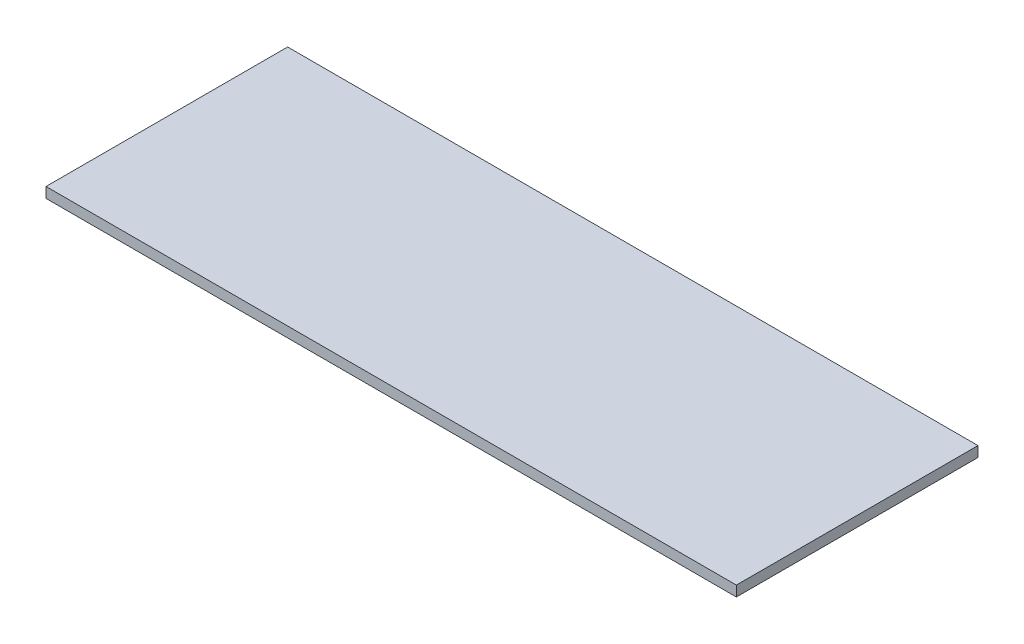
SolidWorks part; units mm, degrees
ref_plane "Front Plane" through (0, 0, 0) normal (0, 0, 1) x (1, 0, 0)
ref_plane "Top Plane" through (0, 0, 0) normal (0, 1, 0) x (1, 0, 0)
ref_plane "Right Plane" through (0, 0, 0) normal (1, 0, 0) x (0, 0, -1)
sketch "Sketch1" plane through (0, 0, 0) normal (0, 1, 0) x (1, 0, 0)
  line L1 (-100, -35) -> (100, -35)
  line L2 (-100, -35) -> (-100, 35)
  line L3 (-100, 35) -> (100, 35)
  line L4 (100, -35) -> (100, 35)
  line L5 (-100, -35) -> (100, 35) construction
  line L6 (-100, 35) -> (100, -35) construction
  point P0 (0, 0)
  dimension "D1" = 200
  dimension "D2" = 70
extrude "Boss-Extrude1" add sketch "Sketch1" along normal blind 3
